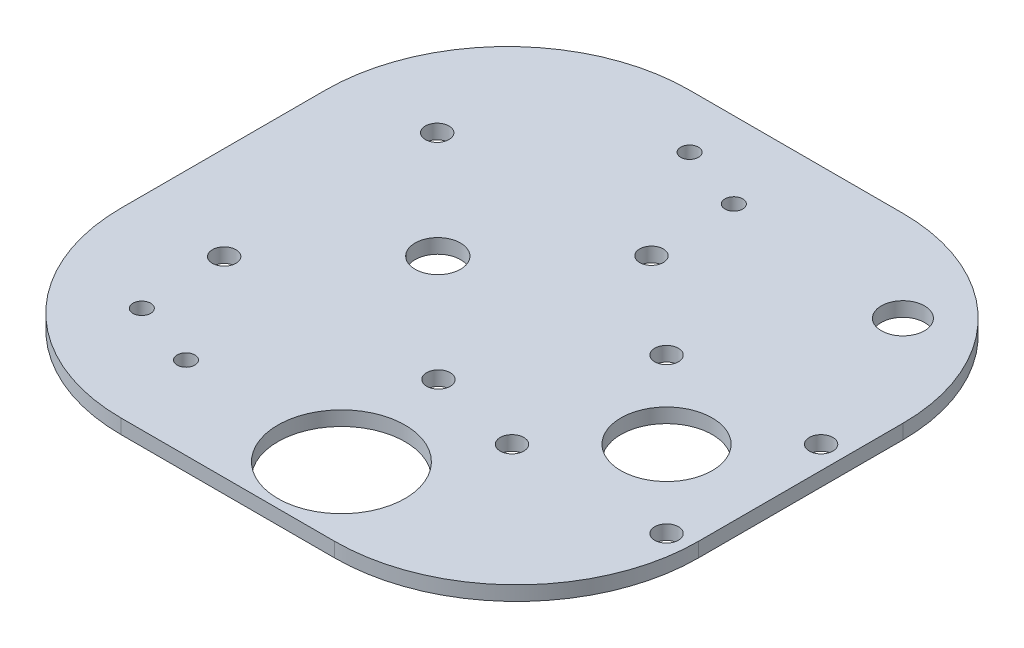
SolidWorks part; units mm, degrees
note: The reader was unsure of these and kept them because the rebuilt part matched: thickness of "Brida base1", "Chapa metálica1", "Chapa metálica6", "Chapa metálica7", "Chapa metálica8", "Chapa metálica9", "Chapa metálica10", "Chapa metálica11".
ref_plane "Alzado" through (0, 0, 0) normal (0, 0, 1) x (1, 0, 0)
ref_plane "Planta" through (0, 0, 0) normal (0, 1, 0) x (1, 0, 0)
ref_plane "Vista lateral" through (0, 0, 0) normal (1, 0, 0) x (0, 0, -1)
sketch "Croquis1" plane through (0, 0, 0) normal (0, 1, 0) x (1, 0, 0)
  line L1 (22, -55) -> (-105, -55)
  line L2 (22, -55) -> (22, 70)
  line L3 (22, 70) -> (-105, 70)
  line L4 (-105, -55) -> (-105, 70)
  dimension "D1" = 22
  dimension "D2" = 55
  dimension "D3" = 105
  dimension "D4" = 70
base flange "Brida base1" sketch "Croquis1" thickness 3.175 reverse thickness direction no parameters "D1"=0.7366
sketch "Croquis11" plane through (0, 0, 0) normal (0, 1, 0) x (1, 0, 0)
  line L1 (17, 17) -> (-17, 17)
  line L2 (17, 17) -> (17, -17)
  line L3 (17, -17) -> (-17, -17)
  line L4 (-17, 17) -> (-17, -17)
  circle A0 centre (0, 0) radius 10.05
  circle A1 centre (0, 0) radius 24.0416 construction
  dimension "D1" = 34
  dimension "D2" = 34
extrude "Cortar-Extruir3" cut sketch "Croquis11" against normal blind 10 contours A0
hole_wizard "Taladro de margen para M51" positions "Croquis13" profile "Croquis12" hole size "M5" standard "Ansi Metric" end condition up to next
sketch "Croquis13" plane through (0, 0, 0) normal (0, 1, 0) x (1, 0, 0)
  line L8 (17, 17) -> (-17, 17)
  line L9 (-17, 17) -> (-17, -17)
  line L10 (-17, -17) -> (17, -17)
  line L11 (17, -17) -> (17, 17)
  line L12 (17, 17) -> (-17, 17)
  line L13 (-17, 17) -> (-17, -17)
  line L14 (-17, -17) -> (17, -17)
  line L15 (17, -17) -> (17, 17)
  circle A2 centre (0, 0) radius 10.05
  circle A3 centre (0, 0) radius 10.05
  point P0 (17, 17)
  point P19 (-17, 17)
  point P21 (-17, -17)
  point P22 (17, -17)
  dimension "D1" = 0
  dimension "D2" = 0
sketch "Croquis12" plane through (17, 0, -17) normal (1, 0, 0) x (0, 0, 1)
  line L0 (0, 0) -> (0, 3.175)
  line L1 (0, 3.175) -> (2.6, 3.175)
  line L2 (2.6, 3.175) -> (2.6, 0)
  line L5 (2.6, 0) -> (0, 0)
  line L11 (0, -6.35) -> (0, 107.95) construction
  dimension "Diámetro de taladro hasta el siguiente" = 5.2
  dimension "Profundidad de taladro hasta el siguiente" = 3.175
hole_wizard "Taladro de margen para M52" positions "Croquis15" profile "Croquis14" hole size "M5" standard "Ansi Metric" end condition up to next
sketch "Croquis15" plane through (0, 0, 0) normal (0, 1, 0) x (1, 0, 0)
  line L0 (0, -60) -> (0, -100) construction
  line L2 (0, -60) -> (0, 0) construction
  line L4 (-17, -17) -> (-61.0066, 10.6841) construction
  line L5 (-28.5232, 33.4035) -> (-37.4348, -12.7439) construction
  point P0 (-37.5787, 34.2559)
  point P11 (-37.4348, -12.7439)
  point P12 (-84.4346, -12.8877)
  point P13 (-84.5784, 34.1121)
  point P14 (-61.0066, 10.6841)
  dimension "D2" = 47
  dimension "D1" = 4
sketch "Croquis14" plane through (-37.5787, 0, -34.2559) normal (1, 0, 0) x (0, 0, 1)
  line L0 (0, 0) -> (0, 3.175)
  line L1 (0, 3.175) -> (2.6, 3.175)
  line L2 (2.6, 3.175) -> (2.6, 0)
  line L5 (2.6, 0) -> (0, 0)
  line L11 (0, -6.35) -> (0, 107.95) construction
  dimension "Diámetro de taladro hasta el siguiente" = 5.2
  dimension "Profundidad de taladro hasta el siguiente" = 3.175
sketch "Croquis16" plane through (0, 0, 0) normal (0, 1, 0) x (1, 0, 0)
  circle A0 centre (-61.0066, 10.6841) radius 5
extrude "Cortar-Extruir4" cut sketch "Croquis16" against normal through all normal cut yes
sketch "Croquis17" plane through (0, 0, 0) normal (0, 1, 0) x (1, 0, 0)
  line L0 (22, 70) -> (-105, 70) construction
  line L1 (22, -55) -> (22, 70) construction
  circle A0 centre (-32.4251, -39.0982) radius 14
  circle A1 centre (2, 50) radius 4.75
  dimension "D1" = 28
  dimension "D2" = 9.5
  dimension "D3" = 20
  dimension "D4" = 20
extrude "Cortar-Extruir5" cut sketch "Croquis17" against normal blind 10 normal cut yes
hole_wizard "Taladro de margen para M3.51" positions "Croquis18" profile "Croquis19" hole size "M3.5" standard "Ansi Metric" end condition through all
sketch "Croquis18" plane through (-235.296, -6.288, -137.5905) normal (0, -1, 0) x (-0.5911, 0, 0.8066)
  point P0 (46.9832, -222.4722)
  point P1 (42.309, -237.2967)
  point P2 (-48.3247, -208.7195)
  point P5 (-43.6505, -193.895)
  point P8 (0, 0)
  point P9 (0, 0)
  point P10 (0, 0)
  point P11 (0, 0)
  point P12 (0, 0)
  point P13 (0, 0)
  point P14 (0, 0)
sketch "Croquis19" plane through (-83.6306, -6.288, 31.817) normal (1, 0, 0) x (0, 0, -1)
  line L0 (0, 0) -> (0, 6.288)
  line L1 (0, 6.288) -> (1.95, 6.288)
  line L2 (1.95, 6.288) -> (1.95, 0)
  line L5 (1.95, 0) -> (0, 0)
  line L11 (0, -6.35) -> (0, 107.95) construction
  dimension "Diámetro de taladro hasta el siguiente" = 3.9
  dimension "Profundidad de taladro hasta el siguiente" = 6.288
fillet "Redondeo1" radius 40 4 edges at (22, -1.5875, -70) (22, -1.5875, 55) (-105, -1.5875, 55) (-105, -1.5875, -70)
sketch "Líneas de pliegue1" plane through (0, 0, 0) normal (0, 1, 0) x (1, 0, 0)
sketch "Cuadro delimitador1" plane through (0, 0, 0) normal (0, 1, 0) x (1, 0, 0)
sheet metal parameters "Chapa metálica1" thickness 3.175 parameters "D1"=0.7366
flat pattern "Chapa desplegada1"
sketch "Líneas de pliegue2" plane through (0, 0, 0) normal (0, 1, 0) x (1, 0, 0)
sketch3d "Cuadro delimitador2"
  line L0 (150.0167, 149.9833, 0) -> (149.9832, -150.0167, 0) construction
  line L1 (-149.9832, 150.0167, 0) -> (-150.0167, -149.9833, 0) construction
  line L2 (150.0167, 149.9833, 0) -> (-149.9832, 150.0167, 0) construction
  line L3 (149.9832, -150.0167, 0) -> (-150.0167, -149.9833, 0) construction
sheet metal parameters "Chapa metálica6" thickness 3.175 parameters "D1"=0.7366, "D7"=6.35
flat pattern "Chapa desplegada1"
sketch "Líneas de pliegue2" plane through (0, 0, 0) normal (0, 1, 0) x (1, 0, 0)
sketch3d "Cuadro delimitador2"
  line L0 (-125.0764, 124.9235, 0) -> (-124.9234, -125.0764, 0) construction
  line L1 (124.9235, 125.0764, 0) -> (125.0764, -124.9235, 0) construction
  line L2 (-125.0764, 124.9235, 0) -> (124.9235, 125.0764, 0) construction
  line L3 (-124.9234, -125.0764, 0) -> (125.0764, -124.9235, 0) construction
sheet metal parameters "Chapa metálica7" thickness 3.175 parameters "D1"=0.7366, "D7"=6.35
flat pattern "Chapa desplegada1"
sketch "Líneas de pliegue2" plane through (0, 0, 0) normal (0, 1, 0) x (1, 0, 0)
sketch3d "Cuadro delimitador2"
  line L0 (-125.0764, 124.9235, 0) -> (-124.9234, -125.0764, 0) construction
  line L1 (124.9235, 125.0764, 0) -> (125.0764, -124.9235, 0) construction
  line L2 (-125.0764, 124.9235, 0) -> (124.9235, 125.0764, 0) construction
  line L3 (-124.9234, -125.0764, 0) -> (125.0764, -124.9235, 0) construction
sheet metal parameters "Chapa metálica8" thickness 3.175 parameters "D1"=0.7366, "D7"=6.35
flat pattern "Chapa desplegada1"
sketch "Líneas de pliegue2" plane through (0, 0, 0) normal (0, 1, 0) x (1, 0, 0)
sketch3d "Cuadro delimitador2"
  line L0 (-135.0675, 134.9324, 0) -> (-134.9325, -135.0675, 0) construction
  line L1 (134.9324, 135.0675, 0) -> (135.0675, -134.9324, 0) construction
  line L2 (-135.0675, 134.9324, 0) -> (134.9324, 135.0675, 0) construction
  line L3 (-134.9325, -135.0675, 0) -> (135.0675, -134.9324, 0) construction
sheet metal parameters "Chapa metálica9" thickness 3.175 parameters "D1"=0.7366, "D7"=6.35
flat pattern "Chapa desplegada1"
sketch "Líneas de pliegue2" plane through (0, 0, 0) normal (0, 1, 0) x (1, 0, 0)
sketch3d "Cuadro delimitador2"
  line L0 (-99, 70, 0) -> (-99, -55, 0) construction
  line L1 (22, 70, 0) -> (22, -55, 0) construction
  line L2 (-99, 70, 0) -> (22, 70, 0) construction
  line L3 (-99, -55, 0) -> (22, -55, 0) construction
sheet metal parameters "Chapa metálica10" thickness 3.175 parameters "D1"=0.7366, "D7"=6.35
flat pattern "Chapa desplegada1"
sketch "Líneas de pliegue2" plane through (0, 0, 0) normal (0, 1, 0) x (1, 0, 0)
sketch3d "Cuadro delimitador2"
  line L0 (22, -55, 0) -> (-105, -55, 0) construction
  line L1 (22, 70, 0) -> (-105, 70, 0) construction
  line L2 (22, -55, 0) -> (22, 70, 0) construction
  line L3 (-105, -55, 0) -> (-105, 70, 0) construction
sheet metal parameters "Chapa metálica11" thickness 3.175 parameters "D1"=0.7366, "D7"=6.35
flat pattern "Chapa desplegada1"
sketch "Líneas de pliegue2" plane through (0, 0, 0) normal (0, 1, 0) x (1, 0, 0)
sketch3d "Cuadro delimitador2"
  line L0 (22, -55, 0) -> (-105, -55, 0) construction
  line L1 (22, 70, 0) -> (-105, 70, 0) construction
  line L2 (22, -55, 0) -> (22, 70, 0) construction
  line L3 (-105, -55, 0) -> (-105, 70, 0) construction
